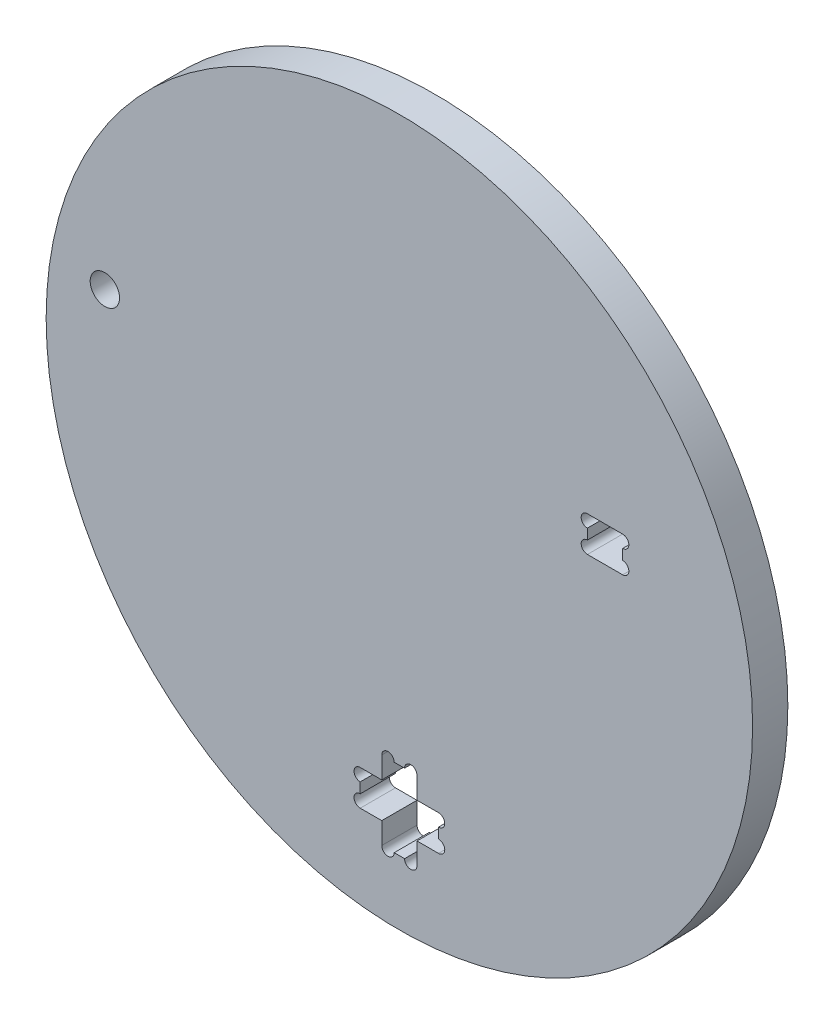
SolidWorks part; units mm, degrees
ref_plane "Piano frontale" through (0, 0, 0) normal (0, 0, 1) x (1, 0, 0)
ref_plane "Piano superiore" through (0, 0, 0) normal (0, 1, 0) x (1, 0, 0)
ref_plane "Piano destro" through (0, 0, 0) normal (1, 0, 0) x (0, 0, -1)
sketch "Schizzo1" plane through (0, 0, 0) normal (0, 0, 1) x (1, 0, 0)
  line L0 (26.3823, 24.0186) -> (55.7751, 24.0186) construction
  line L1 (44.3823, 15.0186) -> (26.3823, 15.0186)
  line L2 (44.3823, 21.3686) -> (44.3823, 26.6686)
  line L3 (44.3823, 33.0186) -> (26.3823, 33.0186)
  line L4 (26.3823, 21.3686) -> (26.3823, 26.6686)
  line L6 (35.3823, 15.0186) -> (35.3823, 39.3689) construction
  line L7 (-66.9974, -126.2343) -> (-72.2974, -126.2343)
  line L8 (-60.6474, -126.2343) -> (-60.6474, -137.2343)
  line L9 (-66.9974, -166.2343) -> (-72.2974, -166.2343)
  line L10 (-78.6474, -126.2343) -> (-78.6474, -137.2343)
  line L12 (-78.6474, -155.2343) -> (-78.6474, -166.2343)
  line L13 (-49.6474, -137.2343) -> (-60.6474, -137.2343)
  line L14 (-49.6474, -143.5843) -> (-49.6474, -148.8843)
  line L15 (-49.6474, -155.2343) -> (-60.6474, -155.2343)
  line L16 (-89.6474, -143.5843) -> (-89.6474, -148.8843)
  line L17 (-78.6474, -155.2343) -> (-89.6474, -155.2343)
  line L19 (-69.6474, -126.2343) -> (-69.6474, -116.1572) construction
  line L22 (-78.6474, -137.2343) -> (-89.6474, -137.2343)
  line L26 (-60.6474, -155.2343) -> (-60.6474, -166.2343)
  arc A0 (44.3823, 15.0186) -> (44.3823, 21.3686) centre (44.3823, 18.1936) ccw
  arc A1 (44.3823, 33.0186) -> (44.3823, 26.6686) centre (44.3823, 29.8436) cw
  arc A2 (26.3823, 33.0186) -> (26.3823, 26.6686) centre (26.3823, 29.8436) ccw
  arc A3 (26.3823, 15.0186) -> (26.3823, 21.3686) centre (26.3823, 18.1936) cw
  arc A4 (-78.6474, -126.2343) -> (-72.2974, -126.2343) centre (-75.4724, -126.2343) cw
  arc A5 (-60.6474, -126.2343) -> (-66.9974, -126.2343) centre (-63.8224, -126.2343) ccw
  arc A6 (-78.6474, -166.2343) -> (-72.2974, -166.2343) centre (-75.4724, -166.2343) ccw
  arc A7 (-60.6474, -166.2343) -> (-66.9974, -166.2343) centre (-63.8224, -166.2343) cw
  circle A8 centre (-220.0749, 8.955) radius 7.5
  circle A9 centre (-69.6474, -18.7286) radius 180.415
  arc A10 (-89.6474, -155.2343) -> (-89.6474, -148.8843) centre (-89.6474, -152.0593) cw
  arc A11 (-89.6474, -137.2343) -> (-89.6474, -143.5843) centre (-89.6474, -140.4093) ccw
  arc A12 (-49.6474, -155.2343) -> (-49.6474, -148.8843) centre (-49.6474, -152.0593) ccw
  arc A13 (-49.6474, -137.2343) -> (-49.6474, -143.5843) centre (-49.6474, -140.4093) cw
  point P7 (-69.6474, -146.2343)
  point P21 (-69.6474, -146.2343)
  point P31 (-394.2396, -185.5702)
  dimension "D9" = 40
  dimension "D10" = 3.175
  dimension "D11" = 3.175
  dimension "D3" = 3.175
  dimension "D4" = 15
  dimension "D5" = 360.83
  dimension "D1" = 18
  dimension "D2" = 18
  dimension "D6" = 18
  dimension "D7" = 40
  dimension "D8" = 18
extrude "Estrusione-Estrusione1" add sketch "Schizzo1" along normal blind 18 contours A9
extrude "Taglio-Estrusione1" cut sketch "Schizzo1<17>" along normal blind 48 contours L3 A2 L4 A3 L1 A0 L2 A1
sketch "Schizzo1<17>" plane through (0, 0, 0) normal (0, 0, 1) x (1, 0, 0) same geometry as "Schizzo1"
extrude "Taglio-Estrusione2" cut sketch "Schizzo1<18>" along normal blind 80 contours A8
sketch "Schizzo1<18>" plane through (0, 0, 0) normal (0, 0, 1) x (1, 0, 0) same geometry as "Schizzo1"
extrude "Taglio-Estrusione3" cut sketch "Schizzo1<19>" along normal blind 135 contours L10 L22 A11 L16 A10 L17 L12 A6 L9 A7 L26 L15 A12 L14 A13 L13 L8 A5 L7 A4
sketch "Schizzo1<19>" plane through (0, 0, 0) normal (0, 0, 1) x (1, 0, 0) same geometry as "Schizzo1"
